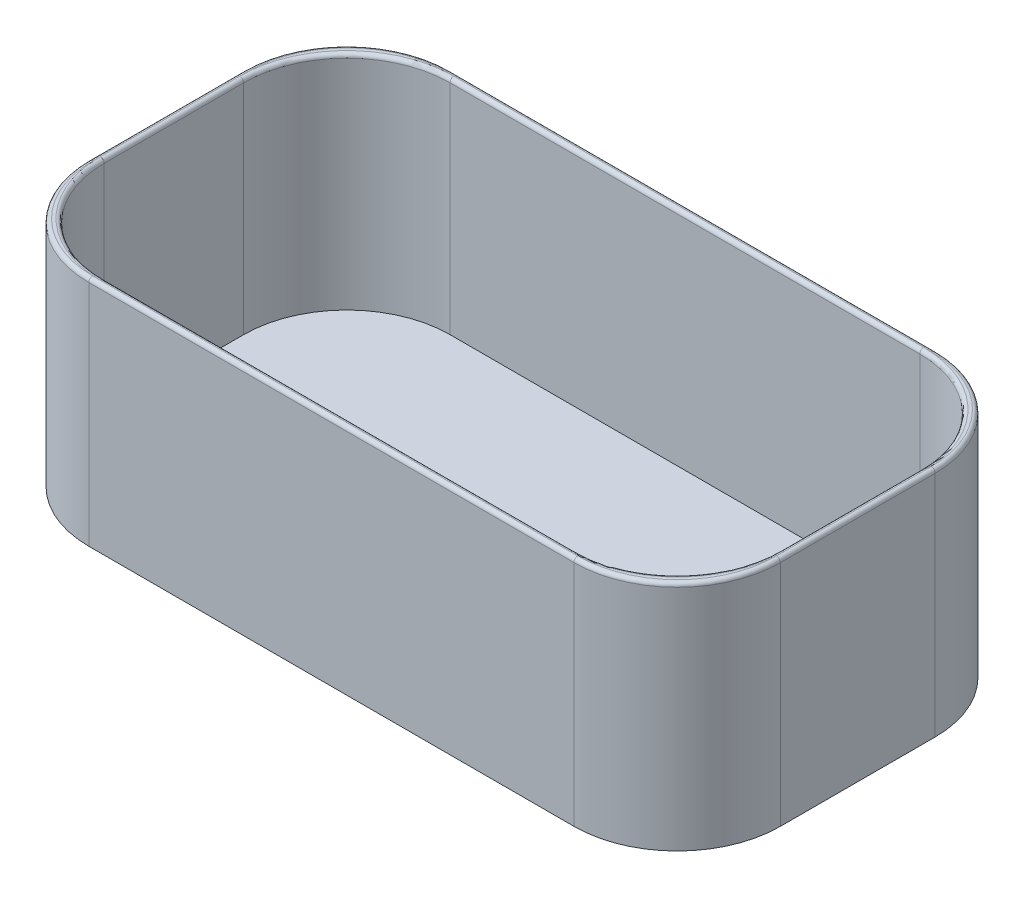
SolidWorks part; units mm, degrees
ref_plane "前视基准面" through (0, 0, 0) normal (0, 0, 1) x (1, 0, 0)
ref_plane "上视基准面" through (0, 0, 0) normal (0, 1, 0) x (1, 0, 0)
ref_plane "右视基准面" through (0, 0, 0) normal (1, 0, 0) x (0, 0, -1)
other "Configuration Table"
sketch "草图1" plane through (0, 0, 0) normal (0, 1, 0) x (1, 0, 0)
  line L1 (-67, -35) -> (67, -35)
  line L2 (-67, -35) -> (-67, 35)
  line L3 (-67, 35) -> (67, 35)
  line L4 (67, -35) -> (67, 35)
  line L5 (-67, -35) -> (67, 35) construction
  line L6 (-67, 35) -> (67, -35) construction
  point P0 (0, 0)
  dimension "D1" = 134
  dimension "D2" = 70
extrude "凸台-拉伸1" add sketch "草图1" along normal blind 45 contours L1 L4 L3 L2
sketch "草图2" plane through (0, 45, 0) normal (0, 1, 0) x (1, 0, 0)
  line L16 (-65.5, 33.5) -> (-65.5, -33.5)
  line L17 (-65.5, -33.5) -> (65.5, -33.5)
  line L18 (65.5, -33.5) -> (65.5, 33.5)
  line L19 (65.5, 33.5) -> (-65.5, 33.5)
  line L20 (-65.5, 33.5) -> (-65.5, -33.5)
  line L21 (-65.5, -33.5) -> (65.5, -33.5)
  line L22 (65.5, -33.5) -> (65.5, 33.5)
  line L23 (65.5, 33.5) -> (-65.5, 33.5)
  dimension "D1" = 1.5
extrude "切除-拉伸1" cut sketch "草图2" against normal offset from surface (43 mm away) 2 up to face at (0, 0, 0)
fillet "圆角1" radius 20 8 edges at (-65.5, 23.5, 33.5) (-67, 22.5, 35) (-67, 22.5, -35) (-65.5, 23.5, -33.5) (65.5, 23.5, -33.5) (65.5, 23.5, 33.5) (67, 22.5, 35) (67, 22.5, -35)
fillet "圆角2" radius 0.75 16 edges at (-61.1421, 45, -29.1421) (0, 45, -35) (61.1421, 45, -29.1421) (67, 45, 0) (61.1421, 45, 29.1421) (0, 45, 35) (-61.1421, 45, 29.1421) (-67, 45, 0) (59.6421, 45, 27.6421) (65.5, 45, 0) (59.6421, 45, -27.6421) (0, 45, -33.5) (-59.6421, 45, -27.6421) (-65.5, 45, 0) (-59.6421, 45, 27.6421) (0, 45, 33.5)
